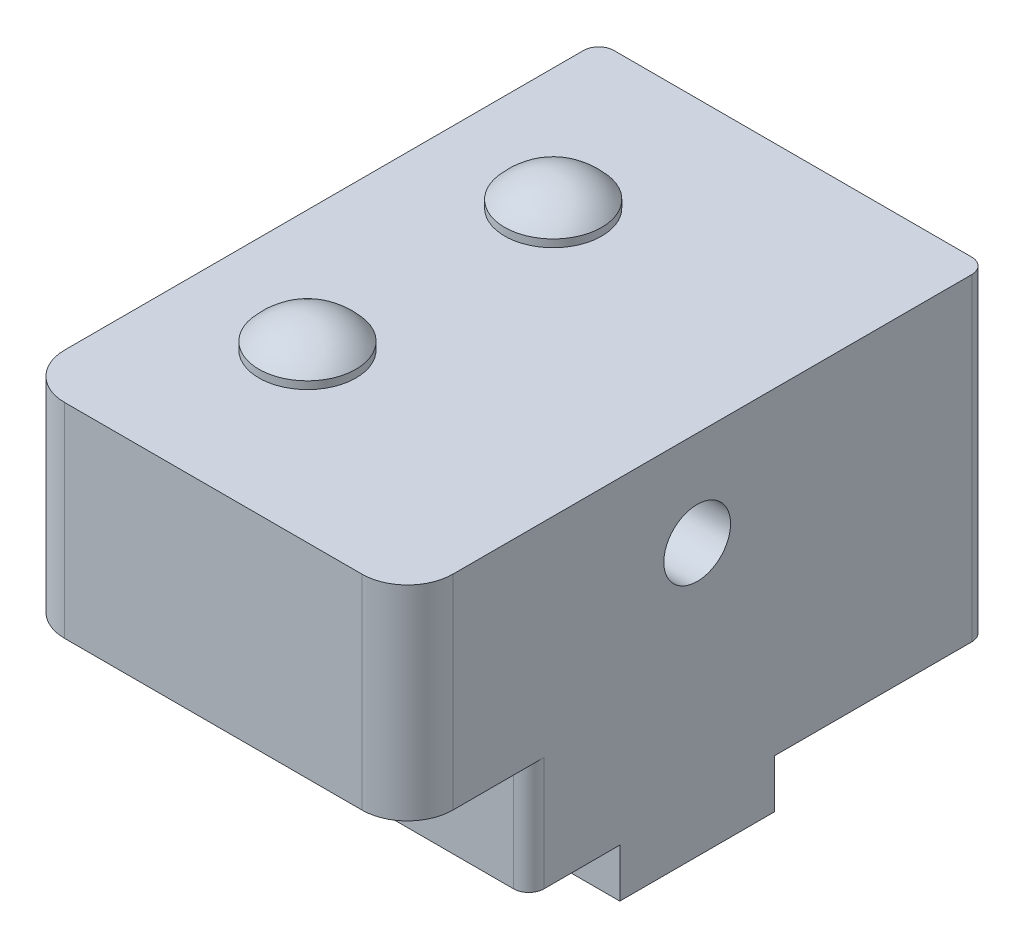
SolidWorks part; units mm, degrees
ref_plane "Front Plane" through (0, 0, 0) normal (0, 0, 1) x (1, 0, 0)
ref_plane "Top Plane" through (0, 0, 0) normal (0, 1, 0) x (1, 0, 0)
ref_plane "Right Plane" through (0, 0, 0) normal (1, 0, 0) x (0, 0, -1)
sketch "Sketch1" plane through (0, 0, 0) normal (0, 1, 0) x (1, 0, 0)
  line L1 (0, 0) -> (25.59, 0)
  line L2 (0, 0) -> (0, 38.2)
  line L3 (0, 38.2) -> (25.59, 38.2)
  line L4 (25.59, 0) -> (25.59, 38.2)
  dimension "D1" = 25.59
  dimension "D2" = 38.2
extrude "Boss-Extrude1" add sketch "Sketch1" along normal blind 20.97
sketch "Sketch2" plane through (0, 0, 0) normal (0, -1, 0) x (1, 0, 0)
  line L0 (0, -19.1) -> (25.59, -19.1) construction
  line L1 (0, -38.2) -> (0, 0) construction
  line L2 (25.59, 0) -> (25.59, -38.2) construction
  line L3 (0, -24.2) -> (0, -14)
  line L4 (0, -14) -> (25.59, -14)
  line L5 (25.59, -14) -> (25.59, -24.2)
  line L6 (0, -24.2) -> (25.59, -24.2)
  point P8 (0, -19.1)
  dimension "D1" = 10.2
extrude "Boss-Extrude2" add sketch "Sketch2" along normal blind 3.2
sketch "Sketch3" plane through (25.59, 0, 0) normal (1, 0, 0) x (0, 0, -1)
  line L0 (0, 0) -> (14, 0) construction
  circle A0 centre (19.1, 14.7) radius 2.2
  dimension "D1" = 4.4
  dimension "D2" = 14.7
extrude "Cut-Extrude1" cut sketch "Sketch3" against normal up to surface (25.59 mm away) up to face at (0, 4.4425, -19.1)
sketch "Sketch4" plane through (0, 0, -38.2) normal (0, 0, -1) x (-1, 0, 0)
  line L0 (-25.59, 20.97) -> (0, 20.97) construction
  line L1 (-25.59, 20.97) -> (-25.59, 0) construction
  line L2 (-25.59, 0) -> (0, 0) construction
  circle A0 centre (-22.59, 17.47) radius 1.25
  circle A1 centre (-22.59, 4.5) radius 1.25
  dimension "D3" = 2.5
  dimension "D6" = 2.5
  dimension "D1" = 3.5
  dimension "D2" = 3
  dimension "D4" = 4.5
  dimension "D5" = 3
extrude "Cut-Extrude2" cut sketch "Sketch4" against normal blind 5
ref_plane "Plane1" through (12.795, 0, 0) normal (1, 0, 0) x (0, 0, -1)
ref_plane "Plane2" through (0, 10.485, 0) normal (0, -1, 0) x (-1, 0, 0)
fillet "Fillet1" radius 1 1 edges at (25.59, 10.485, -38.2)
fillet "Fillet2" radius 1 1 edges at (0, 10.485, -38.2)
fillet "Fillet3" radius 3 2 edges at (0, 10.485, 0) (25.59, 10.485, 0)
sketch "Sketch5" plane through (0, 0, 0) normal (0, -1, 0) x (1, 0, 0)
  line L0 (0, -14) -> (0, -3) construction
  line L1 (0, -8) -> (25.59, -8)
  line L2 (0, -8) -> (0, 0)
  line L3 (0, 0) -> (25.59, 0)
  line L4 (25.59, -8) -> (25.59, 0)
  line L5 (25.59, -14) -> (0, -14) construction
  dimension "D1" = 6
extrude "Cut-Extrude3" cut sketch "Sketch5" against normal blind 7.5
fillet "Fillet4" radius 1 2 edges at (0, 3.75, -8) (25.59, 3.75, -8)
sketch "Sketch6" plane through (0, 20.97, 0) normal (0, 1, 0) x (1, 0, 0)
  line L0 (24.59, 38.2) -> (1, 38.2) construction
  line L1 (0, 37.2) -> (0, 3) construction
  circle A0 centre (8, 27.2) radius 3.2
  dimension "D3" = 6.4
  dimension "D1" = 11
  dimension "D2" = 8
extrude "Boss-Extrude4" add sketch "Sketch6" along normal blind 0.5
ref_plane "Plane4" through (0, 0, -19.1) normal (0, 0, -1) x (-1, 0, 0)
mirror "Mirror3" about plane through (0, 0, -19.1) normal (0, 0, -1) of "Boss-Extrude4"
dome "Dome1" faces to dome 1 distance 1.5 reverse direction no elliptical dome no face at (8, 21.47, -14.2) parameters "D1"=1.5
dome "Dome2" faces to dome 1 distance 1.5 reverse direction no elliptical dome no face at (8, 21.47, -24) parameters "D1"=1.5
mirror "Mirror4" about plane through (12.795, 0, 0) normal (1, 0, 0) of "Cut-Extrude2"
